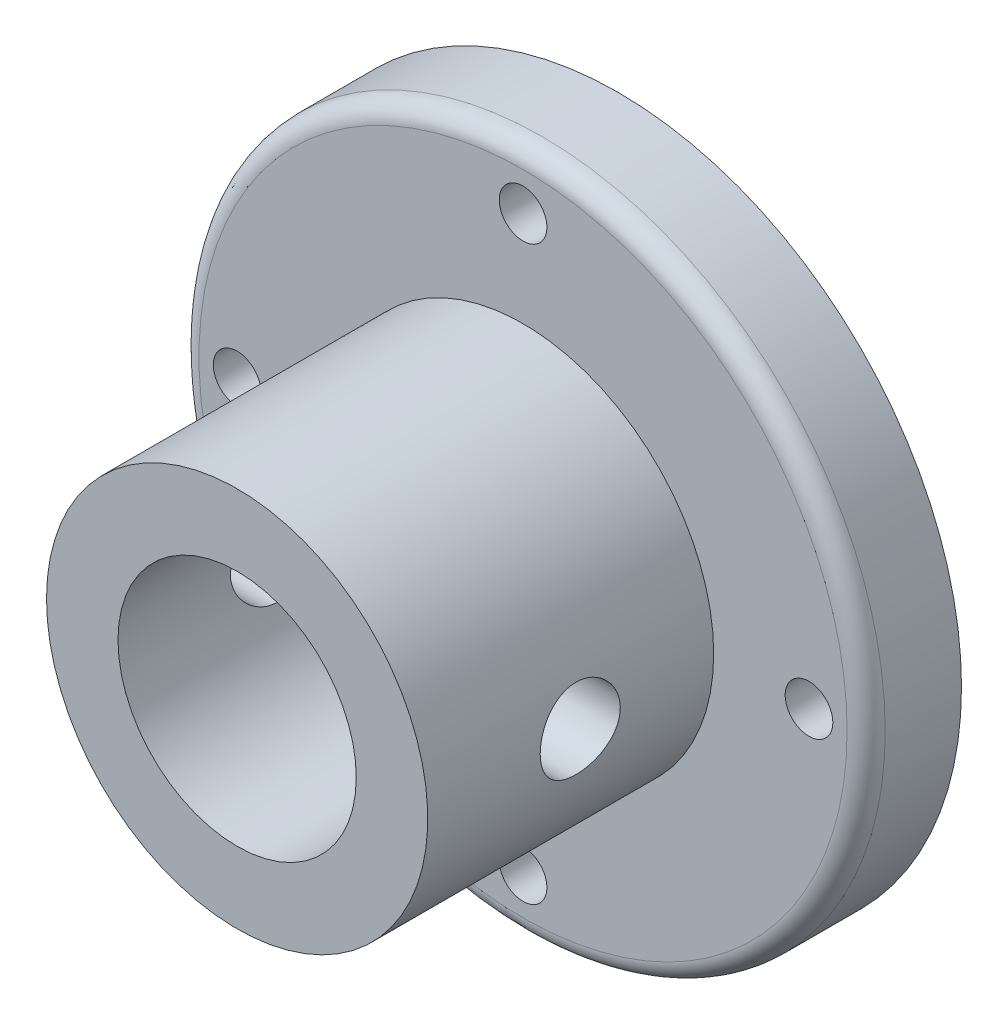
SolidWorks part; units mm, degrees
ref_plane "前视基准面" through (0, 0, 0) normal (0, 0, 1) x (1, 0, 0)
ref_plane "上视基准面" through (0, 0, 0) normal (0, 1, 0) x (1, 0, 0)
ref_plane "右视基准面" through (0, 0, 0) normal (1, 0, 0) x (0, 0, -1)
sketch "草图1" plane through (0, 0, 0) normal (0, 0, 1) x (1, 0, 0)
  line L0 (0, 15) -> (0, -22.7729) construction
  circle A0 centre (0, 0) radius 12
  circle A1 centre (0, 0) radius 18
  circle A2 centre (0, 0) radius 15 construction
  circle A3 centre (0, 15) radius 1.25
  circle A4 centre (-15, 0) radius 1.25
  circle A5 centre (0, -15) radius 1.25
  circle A6 centre (15, 0) radius 1.25
  dimension "D1" = 24
  dimension "D2" = 36
  dimension "D3" = 30
  dimension "D4" = 2.5
  dimension "D5" = 2.5
  dimension "D6" = 2.5
  dimension "D7" = 2.5
extrude "凸台-拉伸1" add sketch "草图1" along normal blind 5
sketch "草图2" plane through (0, 0, 5) normal (0, 0, 1) x (1, 0, 0)
  circle A0 centre (0, 0) radius 12
  circle A1 centre (0, 0) radius 10
  dimension "D1" = 20
extrude "凸台-拉伸2" add sketch "草图2" against normal blind 2
fillet "圆角1" radius 1 1 edges at (18, 0, 5)
sketch "草图3" plane through (0, 0, 3) normal (0, 0, -1) x (-1, 0, 0)
  circle A0 centre (0, 0) radius 10
  circle A1 centre (0, 0) radius 6.25
  dimension "D1" = 12.5
extrude "凸台-拉伸3" add sketch "草图3" against normal blind 17
sketch "草图4" plane through (0, 0, 0) normal (1, 0, 0) x (0, 0, -1)
  circle A0 centre (-12, 0) radius 2.1
  dimension "D2" = 4.2
  dimension "D1" = 12
extrude "切除-拉伸1" cut sketch "草图4" against normal blind 20 and the other way blind 20
